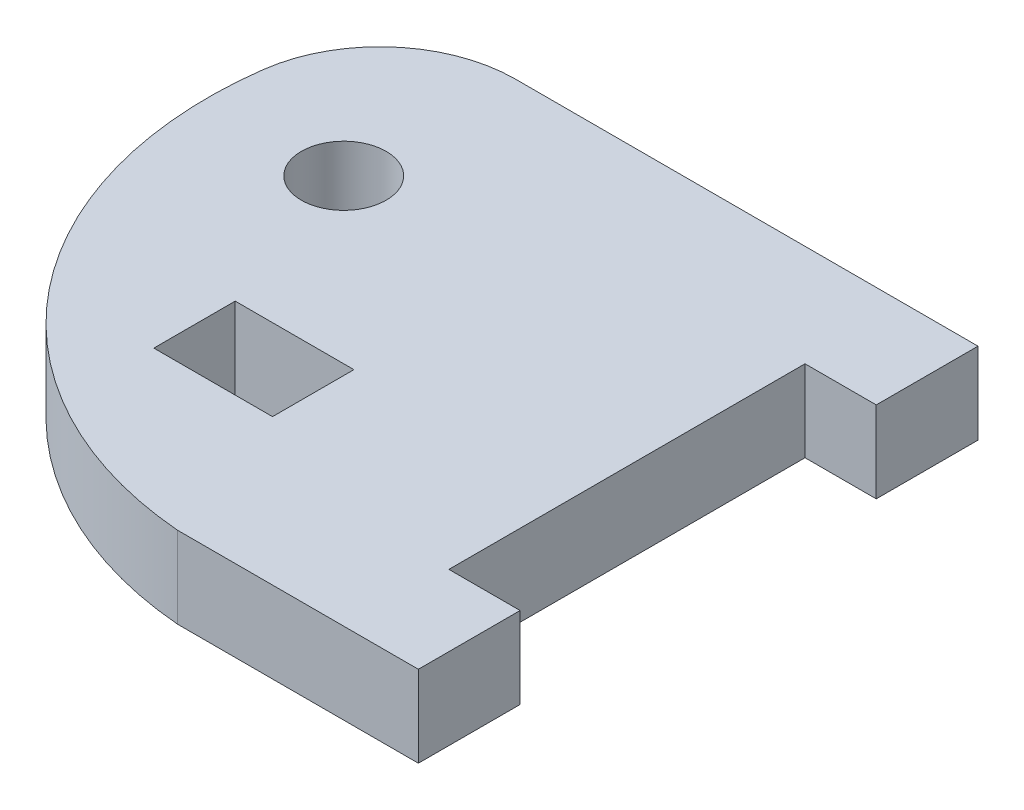
SolidWorks part; units mm, degrees
ref_plane "Front" through (0, 0, 0) normal (0, 0, 1) x (1, 0, 0)
ref_plane "Top" through (0, 0, 0) normal (0, 1, 0) x (1, 0, 0)
ref_plane "Right" through (0, 0, 0) normal (1, 0, 0) x (0, 0, -1)
ref_axis "side-side" through (80.9, 0, 0) along (-1, 0, 0)
ref_axis "up-down" through (0, 50, 0) along (0, -1, 0)
ref_axis "front-back" through (0, 0, -80.9) along (0, 0, 1)
sketch "Sketch1" plane through (0, 0, 0) normal (0, 1, 0) x (1, 0, 0)
  line L0 (29.464, -21.59) -> (29.464, 5.08)
  line L1 (35.56, 0) -> (35.56, -76.5159) construction
  line L2 (34.798, -29.21) -> (16.764, -29.21)
  line L3 (0.1692, 12.7) -> (34.798, 12.7)
  line L5 (29.464, -21.59) -> (34.798, -21.59)
  line L6 (12.954, -12.192) -> (4.064, -12.192)
  line L7 (29.464, 5.08) -> (34.798, 5.08)
  line L8 (34.798, 12.7) -> (34.798, 5.08)
  line L9 (12.954, -12.192) -> (12.954, -18.288)
  line L10 (34.798, -21.59) -> (34.798, -29.21)
  line L11 (12.954, -18.288) -> (4.064, -18.288)
  line L12 (4.064, -12.192) -> (4.064, -18.288)
  arc A0 (16.764, -29.21) -> (-9.901, 3.8878) centre (19.147, 0) cw
  circle A1 centre (0, 0) radius 3.175 construction
  circle A2 centre (0, 0) radius 3.175
  arc A3 (-9.901, 3.8878) -> (0.1692, 12.7) centre (0.1692, 2.54) cw
  dimension "D6" = 10.16
  dimension "D1" = 6.096
  dimension "D2" = 12.7
  dimension "D3" = 41.91
  dimension "D4" = 12.7
  dimension "D5" = 10.16
  dimension "D7" = 0.762
  dimension "D8" = 7.62
extrude "Boss-Extrude1" add sketch "Sketch1" along normal mid plane 6.096
